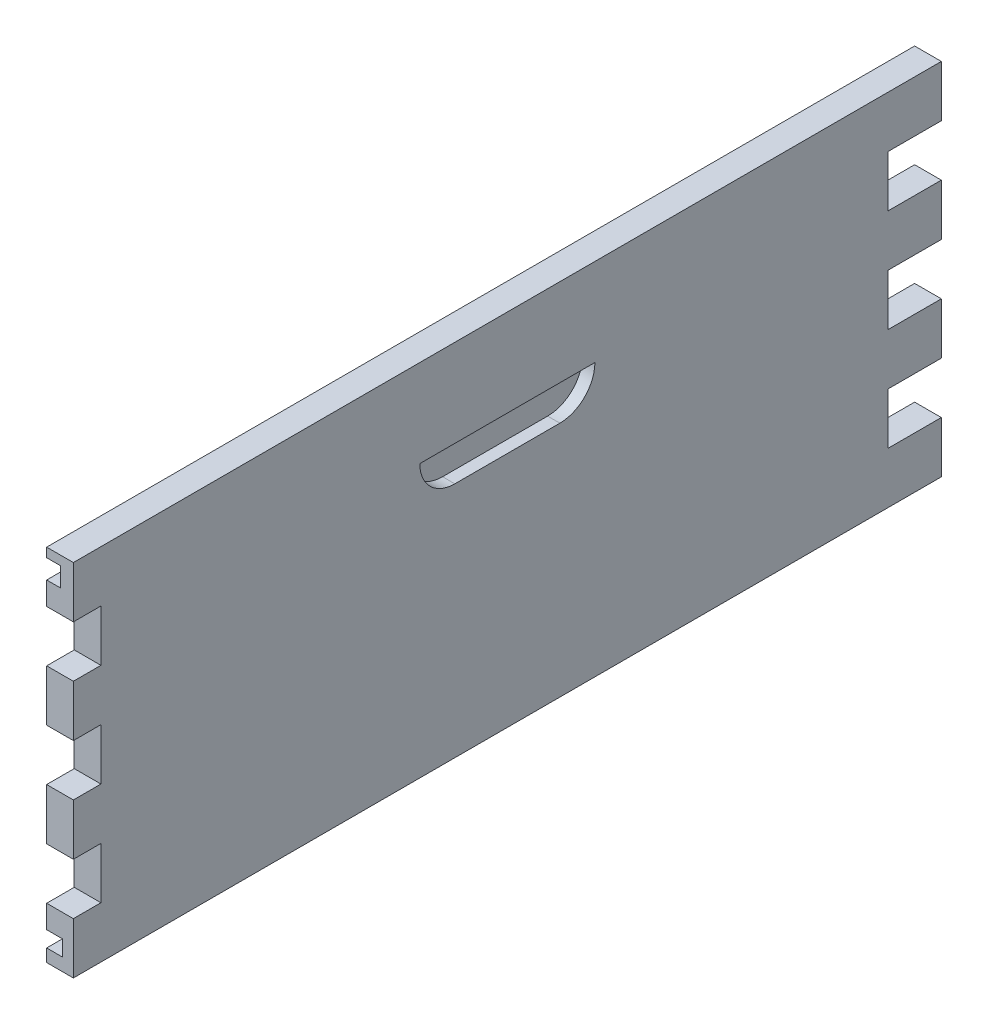
SolidWorks part; units mm, degrees
ref_plane "Plan de face" through (0, 0, 0) normal (0, 0, 1) x (1, 0, 0)
ref_plane "Plan de dessus" through (0, 0, 0) normal (0, 1, 0) x (1, 0, 0)
ref_plane "Plan de droite" through (0, 0, 0) normal (1, 0, 0) x (0, 0, -1)
sketch "Esquisse1" plane through (0, 0, 0) normal (0, 0, 1) x (1, 0, 0)
  line L0 (163.0852, -20.1861) -> (-167.4148, -20.1861) construction
  line L1 (163.0852, 185.3139) -> (147.8352, 185.3139)
  line L2 (163.0852, 185.3139) -> (163.0852, -20.1861)
  line L3 (163.0852, -20.1861) -> (147.8352, -20.1861)
  line L4 (147.8352, 185.3139) -> (147.8352, -20.1861)
  dimension "D1" = 15.25
extrude "Boss.-Extru.1" add sketch "Esquisse1" along normal blind 465.25
sketch "Esquisse2" plane through (163.0852, 0, 0) normal (1, 0, 0) x (0, 0, -1)
  line L0 (30.5, 185.3139) -> (30.5, -20.1861) construction
  line L1 (0, 185.3139) -> (30.5, 185.3139)
  line L2 (0, 185.3139) -> (0, 155.9567)
  line L3 (0, 155.9567) -> (30.5, 155.9567)
  line L4 (30.5, 185.3139) -> (30.5, 155.9567)
  line L5 (0, -20.1861) -> (0, 185.3139) construction
  line L6 (0, 126.5996) -> (30.5, 126.5996)
  line L7 (0, 126.5996) -> (0, 97.2424)
  line L8 (0, 97.2424) -> (30.5, 97.2424)
  line L9 (30.5, 126.5996) -> (30.5, 97.2424)
  line L10 (0, 155.9567) -> (0, 126.5996) construction
  line L11 (0, 67.8853) -> (30.5, 67.8853)
  line L12 (0, 67.8853) -> (0, 38.5282)
  line L13 (0, 38.5282) -> (30.5, 38.5282)
  line L14 (30.5, 67.8853) -> (30.5, 38.5282)
  line L15 (0, -20.1861) -> (30.5, -20.1861)
  line L16 (0, -20.1861) -> (0, 9.171)
  line L17 (0, 9.171) -> (30.5, 9.171)
  line L18 (30.5, -20.1861) -> (30.5, 9.171)
  line L19 (0, 97.2424) -> (0, 67.8853) construction
  line L20 (0, 38.5282) -> (0, 9.171) construction
extrude "Boss.-Extru.2" add sketch "Esquisse2" against normal blind 15.25
sketch "Esquisse3" plane through (163.0852, 0, 0) normal (1, 0, 0) x (0, 0, -1)
  line L0 (-465.25, -20.1861) -> (-465.25, 185.3139) construction
  line L1 (-465.25, 155.9567) -> (-449.5, 155.9567)
  line L2 (-465.25, 155.9567) -> (-465.25, 126.5996)
  line L3 (-465.25, 126.5996) -> (-449.5, 126.5996)
  line L4 (-449.5, 155.9567) -> (-449.5, 126.5996)
  line L5 (-465.25, 126.5996) -> (-465.25, 97.2424) construction
  line L6 (-465.25, 97.2424) -> (-449.5, 97.2424)
  line L7 (-465.25, 97.2424) -> (-465.25, 67.8853)
  line L8 (-465.25, 67.8853) -> (-449.5, 67.8853)
  line L9 (-449.5, 97.2424) -> (-449.5, 67.8853)
  line L10 (-465.25, 38.5282) -> (-449.5, 38.5282)
  line L11 (-465.25, 38.5282) -> (-465.25, 9.171)
  line L12 (-465.25, 9.171) -> (-449.5, 9.171)
  line L13 (-449.5, 38.5282) -> (-449.5, 9.171)
  line L14 (-465.25, 67.8853) -> (-465.25, 38.5282) construction
  line L15 (-465.25, 9.171) -> (-465.25, -20.1861) construction
  line L16 (-465.25, 155.9567) -> (-465.25, 185.3139) construction
  line L17 (0, 155.9567) -> (30.5, 155.9567) construction
  dimension "D1" = 15.75
extrude "Enlèv. mat.-Extru.1" cut sketch "Esquisse3" against normal up to next
sketch "Esquisse4" plane through (163.0852, 0, 0) normal (1, 0, 0) x (0, 0, -1)
  line L0 (-267.375, 135.3139) -> (-167.375, 135.3139)
  line L1 (-247.375, 115.3139) -> (-187.375, 115.3139)
  line L2 (-167.375, 135.3139) -> (-167.375, 185.3139) construction
  line L3 (-465.25, 185.3139) -> (30.5, 185.3139) construction
  line L4 (-267.375, 135.3139) -> (-267.375, 185.3139) construction
  line L5 (-217.375, -20.1861) -> (-217.375, 185.3139) construction
  line L6 (-465.25, -20.1861) -> (30.5, -20.1861) construction
  arc A0 (-267.375, 135.3139) -> (-247.375, 115.3139) centre (-247.375, 135.3139) ccw
  arc A1 (-187.375, 115.3139) -> (-167.375, 135.3139) centre (-187.375, 135.3139) ccw
  dimension "D1" = 20
  dimension "D2" = 50
  dimension "D3" = 100
extrude "Enlèv. mat.-Extru.2" cut sketch "Esquisse4" against normal blind 7
sketch "Esquisse5" plane through (0, 0, 465.25) normal (0, 0, 1) x (1, 0, 0)
  line L0 (147.8352, 185.3139) -> (147.8352, 155.9567) construction
  line L1 (147.8352, 169.0639) -> (155.8352, 169.0639)
  line L2 (147.8352, 169.0639) -> (147.8352, 180.0639)
  line L3 (147.8352, 180.0639) -> (155.8352, 180.0639)
  line L4 (155.8352, 169.0639) -> (155.8352, 180.0639)
  line L5 (-152.1648, 170.0639) -> (147.8352, 170.0639) construction
  dimension "D1" = 11
  dimension "D2" = 1
  dimension "D3" = 8
extrude "Enlèv. mat.-Extru.3" cut sketch "Esquisse5" against normal blind 160
sketch "Esquisse6" plane through (0, 0, 465.25) normal (0, 0, 1) x (1, 0, 0)
  line L0 (147.8352, 9.171) -> (147.8352, -20.1861) construction
  line L1 (147.8352, -3.9361) -> (157.0125, -3.9361)
  line L2 (147.8352, -3.9361) -> (147.8352, -12.9361)
  line L3 (147.8352, -12.9361) -> (157.0125, -12.9361)
  line L4 (157.0125, -3.9361) -> (157.0125, -12.9361)
  line L5 (156.0125, -11.9361) -> (156.0125, -4.9361) construction
  line L6 (147.8352, -11.9361) -> (156.0125, -11.9361) construction
  line L7 (-160.1648, -4.9361) -> (156.0125, -4.9361) construction
  dimension "D1" = 1
  dimension "D2" = 1
  dimension "D3" = 1
extrude "Enlèv. mat.-Extru.4" cut sketch "Esquisse6" against normal offset from surface (415.75 mm away) 80 contours L4 L3 L2 L1 up to face at (155.4602, -5.5076, -30.5)
sketch "Esquisse7" plane through (0, -3.9361, 0) normal (0, -1, 0) x (1, 0, 0)
  line L0 (157.0125, 49.5) -> (157.0125, 465.25) construction
  circle A0 centre (29.5125, 49.5) radius 127.5
  dimension "D1" = 255
extrude "Enlèv. mat.-Extru.5" cut sketch "Esquisse7" along normal blind 9
sketch "Esquisse8" plane through (0, 169.0639, 0) normal (0, 1, 0) x (1, 0, 0)
  line L0 (155.8352, -305.25) -> (155.8352, -465.25) construction
  line L1 (147.8352, -305.25) -> (155.8352, -305.25)
  line L2 (155.8352, -305.25) -> (155.8352, -332.9224)
  circle A0 centre (103.975, -332.9224) radius 51.8601 construction
  arc A1 (147.8352, -305.25) -> (155.8352, -332.9224) centre (103.975, -332.9224) cw
extrude "Boss.-Extru.3" add sketch "Esquisse8" along normal up to next
